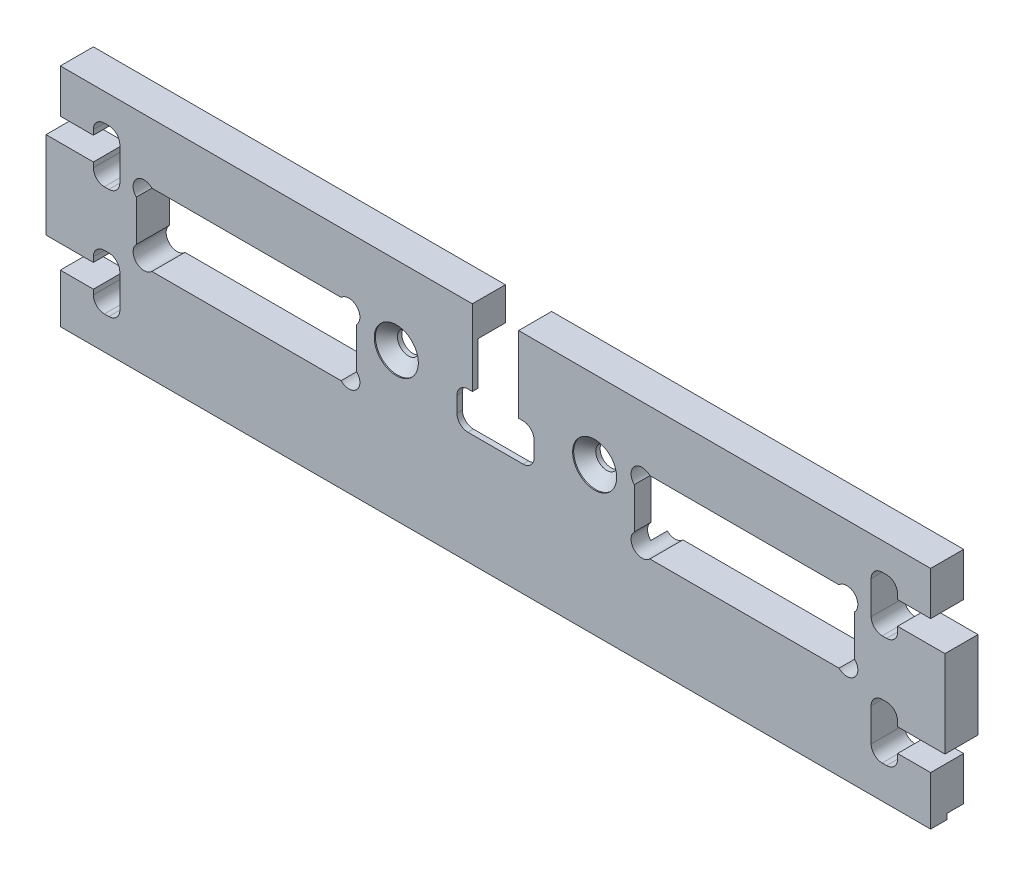
SolidWorks part; units mm, degrees
ref_plane "Front Plane" through (0, 0, 0) normal (0, 0, 1) x (1, 0, 0)
ref_plane "Top Plane" through (0, 0, 0) normal (0, 1, 0) x (1, 0, 0)
ref_plane "Right Plane" through (0, 0, 0) normal (1, 0, 0) x (0, 0, -1)
sketch "Sketch1" plane through (0, 0, 0) normal (0, 0, 1) x (1, 0, 0)
  line L0 (-39.5, 0) -> (39.5, 0) construction
  line L1 (-39.5, 10) -> (39.5, 10)
  line L2 (-39.5, 10) -> (-39.5, -10)
  line L3 (-39.5, -10) -> (39.5, -10)
  line L4 (39.5, 10) -> (39.5, -10)
  line L5 (-39.5, 10) -> (39.5, -10) construction
  line L6 (-39.5, -10) -> (39.5, 10) construction
  line L7 (0, 10) -> (0, -10) construction
  line L9 (-40.8, -3.95) -> (-39.5, -3.95)
  line L10 (-40.8, -3.95) -> (-40.8, 3.95)
  line L11 (-40.8, 3.95) -> (-39.5, 3.95)
  line L12 (-39.5, -3.95) -> (-39.5, 3.95)
  line L13 (-40.8, -3.95) -> (-39.5, 3.95) construction
  line L14 (-40.8, 3.95) -> (-39.5, -3.95) construction
  line L16 (40.8, 3.95) -> (39.5, 3.95)
  line L17 (40.8, -3.95) -> (40.8, 3.95)
  line L18 (40.8, -3.95) -> (39.5, -3.95)
  line L19 (-39.5, 5) -> (39.5, 5) construction
  line L20 (-35.3, 7.5) -> (-35.3, 2.5) construction
  line L21 (-36.5, 3.95) -> (-39.5, 3.95)
  line L22 (-36.5, 3.95) -> (-36.5, 6.05)
  line L23 (-36.5, 6.05) -> (-39.5, 6.05)
  line L24 (-39.5, 3.95) -> (-39.5, 6.05)
  line L25 (-36.5, 3.95) -> (-39.5, 6.05) construction
  line L26 (-36.5, 6.05) -> (-39.5, 3.95) construction
  line L27 (-34.1, 7.5) -> (-36.5, 7.5)
  line L28 (-34.1, 7.5) -> (-34.1, 2.5)
  line L29 (-34.1, 2.5) -> (-36.5, 2.5)
  line L30 (-36.5, 7.5) -> (-36.5, 2.5)
  line L31 (-34.1, 7.5) -> (-36.5, 2.5) construction
  line L32 (-34.1, 2.5) -> (-36.5, 7.5) construction
  line L33 (-34.1, -7.5) -> (-36.5, -7.5)
  line L34 (-34.1, -7.5) -> (-34.1, -2.5)
  line L35 (-34.1, -2.5) -> (-36.5, -2.5)
  line L36 (-36.5, -7.5) -> (-36.5, -2.5)
  line L37 (-36.5, -3.95) -> (-39.5, -3.95)
  line L38 (-36.5, -6.05) -> (-39.5, -6.05)
  line L39 (36.5, 3.95) -> (39.5, 3.95)
  line L40 (36.5, 6.05) -> (39.5, 6.05)
  line L41 (36.5, 7.5) -> (36.5, 2.5)
  line L42 (34.1, 7.5) -> (36.5, 7.5)
  line L43 (34.1, 7.5) -> (34.1, 2.5)
  line L44 (34.1, 2.5) -> (36.5, 2.5)
  line L45 (34.1, -2.5) -> (36.5, -2.5)
  line L46 (34.1, -7.5) -> (34.1, -2.5)
  line L47 (34.1, -7.5) -> (36.5, -7.5)
  line L48 (36.5, -7.5) -> (36.5, -2.5)
  line L49 (36.5, -6.05) -> (39.5, -6.05)
  line L50 (36.5, -3.95) -> (39.5, -3.95)
  point P0 (0, 0)
  point P10 (-40.15, 0)
  point P15 (-38, 5)
  point P35 (-35.3, 5)
  dimension "D1" = 79
  dimension "D2" = 20
  dimension "D4" = 1.3
  dimension "D7" = 5
  dimension "D8" = 2.1
  dimension "D9" = 3
  dimension "D10" = 2.4
  dimension "D11" = 5
extrude "Base shape" add sketch "Sketch1" along normal blind 3 contours L4 L1 L2 L3 | L9 L2 L11 L10 | L16 L4 L18 L17 region at (0, 0, 0) region at (-40.15, 0, 0) region at (40.15, 0, 0)
sketch "Sketch4" plane through (0, -10, 0) normal (0, -1, 0) x (1, 0, 0)
  line L0 (39.5, 3) -> (39.5, 0) construction
  line L1 (-39.5, 3) -> (39.5, 3)
  line L2 (-39.5, 3) -> (-39.5, 1.5)
  line L3 (-39.5, 1.5) -> (39.5, 1.5)
  line L4 (39.5, 3) -> (39.5, 1.5)
extrude "Floor lip" add sketch "Sketch4" along normal blind 0.5
sketch "Sketch6" plane through (0, 0, 0) normal (0, 0, -1) x (-1, 0, 0)
  line L0 (0, 0) -> (0, -10) construction
  line L1 (39.5, -10) -> (-39.5, -10) construction
  line L2 (-4, -10) -> (4, -10) construction
  line L3 (39.5, -10) -> (-39.5, -10) construction
  line L4 (-4, -9) -> (4, -9)
  line L5 (-4, -11) -> (4, -11)
  arc A0 (-4, -9) -> (-4, -11) centre (-4, -10) ccw
  arc A1 (4, -11) -> (4, -9) centre (4, -10) ccw
  point P9 (0, -10)
  dimension "D1" = 2
  dimension "D2" = 8
extrude "Nail cutout" cut sketch "Sketch6" against normal up to surface (1.5 mm away) up to face at (0, -10.25, 1.5)
sketch "Sketch3" plane through (-40.8, 0, 0) normal (-1, 0, 0) x (0, 0, 1)
  line L0 (0, 6.05) -> (3, 3.95) construction
  line L1 (0, 6.05) -> (3, 6.05)
  line L2 (0, 6.05) -> (0, 3.95)
  line L3 (0, 3.95) -> (3, 3.95)
  line L4 (3, 6.05) -> (3, 3.95)
  line L5 (0, -3.95) -> (3, -6.05) construction
  line L6 (0, -3.95) -> (3, -3.95)
  line L7 (0, -3.95) -> (0, -6.05)
  line L8 (0, -6.05) -> (3, -6.05)
  line L9 (3, -3.95) -> (3, -6.05)
  point P6 (1.5, 5)
  point P13 (1.5, -5)
ref_axis "Tap axis top" through (-53.7846, 5, 1.5) along (1, 0, 0)
ref_axis "Tap axis bottom" through (-54.2844, -5, 1.5) along (1, 0, 0)
fillet "Mill fillets" radius 1 16 edges at (36.5, -7.5, 1.5) (36.5, 2.5, 1.5) (34.1, 2.5, 1.5) (34.1, -7.5, 1.5) (36.5, -2.5, 1.5) (36.5, 7.5, 1.5) (34.1, -2.5, 1.5) (34.1, 7.5, 1.5) (-36.5, -2.5, 1.5) (-34.1, -2.5, 1.5) (-34.1, -7.5, 1.5) (-36.5, -7.5, 1.5) (-36.5, 2.5, 1.5) (-34.1, 2.5, 1.5) (-34.1, 7.5, 1.5) (-36.5, 7.5, 1.5)
sketch "Sketch8" [suppressed] plane through (0, 0, 3) normal (0, 0, 1) x (1, 0, 0)
  line L0 (-40.8, 0) -> (40.8, 0) construction
  line L1 (-40.8, -3.95) -> (-40.8, 3.95) construction
  line L2 (40.8, -3.95) -> (40.8, 3.95) construction
  line L4 (-24.5, 5.15) -> (24.5, 5.15)
  line L5 (-25.5, 4.15) -> (-25.5, -4.15)
  line L6 (-24.5, -5.15) -> (24.5, -5.15)
  line L7 (25.5, 4.15) -> (25.5, -4.15)
  line L8 (-25.5, 5.15) -> (25.5, -5.15) construction
  line L9 (-25.5, -5.15) -> (25.5, 5.15) construction
  arc A0 (24.5, -5.15) -> (25.5, -4.15) centre (24.5, -4.15) ccw
  arc A1 (24.5, 5.15) -> (25.5, 4.15) centre (24.5, 4.15) cw
  arc A2 (-25.5, -4.15) -> (-24.5, -5.15) centre (-24.5, -4.15) ccw
  arc A3 (-24.5, 5.15) -> (-25.5, 4.15) centre (-24.5, 4.15) ccw
  point P6 (0, 0)
  dimension "D3" = 1
  dimension "D1" = 51
  dimension "D2" = 10.3
extrude "Led strip pocket" [suppressed] cut sketch "Sketch8" against normal offset from surface (2.5 mm away) 0.5 up to face at (0, -0.6712, 0)
sketch "Sketch9" [suppressed] plane through (0, 0, 0.5) normal (0, 0, 1) x (1, 0, 0)
  line L0 (-19.5, 5.15) -> (-19.5, -5.15)
  line L1 (0, 5.15) -> (0, -5.15) construction
  line L2 (19.5, 5.15) -> (19.5, -5.15)
  line L3 (-25.5, -2.978) -> (25.5, -2.978) construction
  line L4 (25.5, -4.15) -> (25.5, 4.15)
  line L5 (24.5, 5.15) -> (-24.5, 5.15)
  line L6 (-25.5, 4.15) -> (-25.5, -4.15)
  line L7 (-24.5, -5.15) -> (24.5, -5.15)
  line L8 (25.5, -4.15) -> (25.5, 4.15)
  line L9 (24.5, 5.15) -> (-24.5, 5.15)
  line L10 (-25.5, 4.15) -> (-25.5, -4.15)
  line L11 (-24.5, -5.15) -> (24.5, -5.15)
  circle A0 centre (-12.7, -2.978) radius 1
  circle A1 centre (12.7, -2.978) radius 1
  arc A4 (24.5, -5.15) -> (25.5, -4.15) centre (24.5, -4.15) ccw
  arc A5 (25.5, 4.15) -> (24.5, 5.15) centre (24.5, 4.15) ccw
  arc A6 (-24.5, 5.15) -> (-25.5, 4.15) centre (-24.5, 4.15) ccw
  arc A7 (-25.5, -4.15) -> (-24.5, -5.15) centre (-24.5, -4.15) ccw
  arc A8 (24.5, -5.15) -> (25.5, -4.15) centre (24.5, -4.15) ccw
  arc A9 (25.5, 4.15) -> (24.5, 5.15) centre (24.5, 4.15) ccw
  arc A10 (-24.5, 5.15) -> (-25.5, 4.15) centre (-24.5, 4.15) ccw
  arc A11 (-25.5, -4.15) -> (-24.5, -5.15) centre (-24.5, -4.15) ccw
  arc M13 (24.5, -5.15) -> (25.5, -4.15) centre (24.5, -4.15) ccw
  line M14 (25.5, -4.15) -> (25.5, 4.15)
  arc M15 (25.5, 4.15) -> (24.5, 5.15) centre (24.5, 4.15) ccw
  line M16 (24.5, 5.15) -> (-24.5, 5.15)
  arc M17 (-24.5, 5.15) -> (-25.5, 4.15) centre (-24.5, 4.15) ccw
  line M18 (-25.5, 4.15) -> (-25.5, -4.15)
  arc M19 (-25.5, -4.15) -> (-24.5, -5.15) centre (-24.5, -4.15) ccw
  line M20 (-24.5, -5.15) -> (24.5, -5.15)
  dimension "D4" = 2
  dimension "D2" = 6
  dimension "D3" = 8.128
  dimension "D5" = 25.4
  dimension "D1" = 0
extrude "Led strip cuts" [suppressed] cut sketch "Sketch9" against normal up to next contours L0 M16 M17 M18 M19 M20 | L2 M16 M20 M13 M14 M15 | A0 | A1
fillet "Led strip cut fillets" [suppressed] radius 1
sketch "Sketch13" plane through (0, 0, 0) normal (0, 0, -1) x (-1, 0, 0)
  line L0 (0, 15.8648) -> (0, -21.9195) construction
  line L2 (-4.1, -5.7) -> (4.1, -5.7)
  line L3 (-5.1, -4.7) -> (-5.1, 6)
  line L4 (-4.1, 7) -> (4.1, 7)
  line L5 (5.1, -4.7) -> (5.1, 6)
  line L6 (-5.1, -5.7) -> (5.1, 7) construction
  line L7 (-5.1, 7) -> (5.1, -5.7) construction
  line L10 (39.5, 10) -> (-39.5, 10) construction
  arc A0 (-4.1, -5.7) -> (-5.1, -4.7) centre (-4.1, -4.7) cw
  arc A1 (4.1, -5.7) -> (5.1, -4.7) centre (4.1, -4.7) ccw
  arc A4 (5.1, 6) -> (4.1, 7) centre (4.1, 6) ccw
  arc A5 (-5.1, 6) -> (-4.1, 7) centre (-4.1, 6) cw
  point P1 (0, 0.65)
  point P8 (0, 0)
  point P9 (5.5684, 9.0125)
  point P16 (0, 0)
  point P17 (0, 0)
  dimension "D4" = 1
  dimension "D5" = 1
  dimension "D1" = 10.2
  dimension "D2" = 12.7
  dimension "D3" = 3
extrude "Bumper mount inner cut" cut sketch "Sketch13" against normal offset from surface (2.5 mm away) 0.5 up to face at (0, -0.0192, 3)
sketch "Sketch14" plane through (0, 0, 0) normal (0, 0, -1) x (-1, 0, 0)
  line L1 (0, 12.9528) -> (0, -14.0841) construction
  line L2 (4.1, 7) -> (-4.1, 7) construction
  line L3 (-4.1, -5.7) -> (4.1, -5.7) construction
  line L4 (-11.6, 7) -> (11.6, 7)
  line L5 (-12.6, 6) -> (-12.6, -4.7)
  line L6 (-11.6, -5.7) -> (11.6, -5.7)
  line L7 (12.6, 6) -> (12.6, -4.7)
  line L8 (-12.6, 7) -> (12.6, -5.7) construction
  line L9 (-12.6, -5.7) -> (12.6, 7) construction
  arc A1 (11.6, -5.7) -> (12.6, -4.7) centre (11.6, -4.7) ccw
  arc A2 (-12.6, -4.7) -> (-11.6, -5.7) centre (-11.6, -4.7) ccw
  arc A3 (11.6, 7) -> (12.6, 6) centre (11.6, 6) cw
  arc A4 (-12.6, 6) -> (-11.6, 7) centre (-11.6, 6) cw
  point P6 (0, 0.65)
  dimension "D2" = 1
  dimension "D3" = 1
  dimension "D1" = 25.2
extrude "Bumper mount outer cut" cut sketch "Sketch14" against normal blind 1.5
sketch "Sketch15" plane through (0, 0, 1.5) normal (0, 0, -1) x (-1, 0, 0)
  line L0 (-12.6, 2.9) -> (12.6, 2.9) construction
  line L3 (0, 16.4744) -> (0, -20.0474) construction
  line L7 (-12.6, 6) -> (-12.6, -4.7) construction
  line L8 (12.6, -4.7) -> (12.6, 6) construction
  line L11 (-4.1, 7) -> (-11.6, 7) construction
  circle A0 centre (-9, 2.9) radius 1
  circle A1 centre (9, 2.9) radius 1
  point P5 (10, 7)
  point P13 (0, 0)
  point P19 (0, 0)
  point P22 (0, 0)
  point P24 (0, 0)
  point P25 (8.6174, -5.7)
  point P26 (0, 0)
  point P27 (0, 0)
  point P28 (0, 0)
  point P29 (0, 0)
  point P30 (13.4221, 7)
  dimension "D1" = 18
  dimension "D2" = 2
  dimension "D3" = 4.1
extrude "Bumper mount screw holes" cut sketch "Sketch15" against normal up to next
sketch "Sketch16" plane through (0, 0, 2.5) normal (0, 0, -1) x (-1, 0, 0)
  line L0 (-5.1, 1.4) -> (5.1, 1.4) construction
  line L3 (0, 7) -> (0, -4.2) construction
  line L4 (-2.5, 3.1) -> (2.5, 3.1)
  line L5 (-3.5, 2.1) -> (-3.5, 0.7)
  line L6 (-2.5, -0.3) -> (2.5, -0.3)
  line L7 (3.5, 2.1) -> (3.5, 0.7)
  line L8 (-3.5, 3.1) -> (3.5, -0.3) construction
  line L9 (-3.5, -0.3) -> (3.5, 3.1) construction
  line L11 (-5.1, 6) -> (-5.1, -4.7) construction
  line L13 (4.1, 7) -> (-4.1, 7) construction
  arc A0 (2.5, -0.3) -> (3.5, 0.7) centre (2.5, 0.7) ccw
  arc A1 (-3.5, 0.7) -> (-2.5, -0.3) centre (-2.5, 0.7) ccw
  arc A2 (-2.5, 3.1) -> (-3.5, 2.1) centre (-2.5, 2.1) ccw
  arc A3 (2.5, 3.1) -> (3.5, 2.1) centre (2.5, 2.1) cw
  point P2 (0, 0)
  point P5 (0, 0)
  point P6 (0, 1.4)
  point P23 (0, 0)
  point P24 (0, 7.9459)
  point P29 (0, 0)
  dimension "D3" = 1
  dimension "D1" = 7
  dimension "D2" = 3.4
  dimension "D4" = 11.2
extrude "Bumper body cut" cut sketch "Sketch16" against normal up to next
hole_wizard "Bumper screw countersunks" positions "Sketch17" profile "Sketch18" countersink size "M2" standard "ANSI Metric" end condition through all
sketch "Sketch17" plane through (0, 0, 3) normal (0, 0, 1) x (1, 0, 0)
  point P0 (9, 2.9)
  point P3 (-9, 2.9)
sketch "Sketch18" plane through (9, 2.9, 3) normal (1, 0, 0) x (0, -1, 0)
  line L0 (0, 0) -> (0, 3)
  line L1 (0, 3) -> (1, 3)
  line L2 (1, 3) -> (1, 1.1)
  line L3 (1, 1.1) -> (2, 0.1)
  line L4 (2, 0.1) -> (2, 0)
  line L6 (2, 0) -> (0, 0)
  line L7 (-1, 1.1) -> (-2, 0.1) construction
  line L11 (0, -6.35) -> (0, 107.95) construction
  dimension "Thru Hole Dia." = 2
  dimension "Thru Hole Depth" = 3
  dimension "C'Sink Dia." = 4
  dimension "C'Sink Angle" = 90
  dimension "Head Clearance" = 0.1
sketch "Sketch19" plane through (0, 0, 0) normal (0, 0, -1) x (-1, 0, 0)
  line L0 (0, 15.6498) -> (0, -12.9575) construction
  line L1 (39.5, 10) -> (-39.5, 10) construction
  line L2 (-2.1, 3.1) -> (2.1, 3.1)
  line L3 (-2.1, 3.1) -> (-2.1, 10)
  line L4 (-2.1, 10) -> (2.1, 10)
  line L5 (2.1, 3.1) -> (2.1, 10)
  line L6 (-2.1, 3.1) -> (2.1, 10) construction
  line L7 (-2.1, 10) -> (2.1, 3.1) construction
  line L8 (2.5, 3.1) -> (-2.5, 3.1) construction
  point P1 (0, 6.55)
  dimension "D1" = 4.2
extrude "Bumper insertion cut" cut sketch "Sketch19" against normal up to next
sketch "Sketch20" plane through (0, 0, 0) normal (0, 0, -1) x (-1, 0, 0)
  line L0 (-12.6, 6) -> (-12.6, -4.7) construction
  line L1 (-12.6, 4.55) -> (-32.6, 4.55)
  line L2 (-12.6, 4.55) -> (-12.6, -2)
  line L3 (-12.6, -2) -> (-32.6, -2)
  line L4 (-32.6, 4.55) -> (-32.6, -2)
  line L5 (-2.1, 10) -> (-39.5, 10) construction
  line L6 (-12.6, 4.55) -> (-19.15, -2) construction
  line L7 (-22.6, 4.55) -> (-22.6, -2) construction
  line L8 (-32.6, 1.275) -> (-12.6, 1.275) construction
  line L9 (0, 16.176) -> (0, -15.99) construction
  line L10 (12.6, 4.55) -> (12.6, -2)
  line L11 (12.6, -2) -> (32.6, -2)
  line L12 (32.6, 4.55) -> (32.6, -2)
  line L13 (12.6, 4.55) -> (32.6, 4.55)
  circle A0 centre (-13.3071, 3.8429) radius 1
  circle A1 centre (-31.8929, 3.8429) radius 1
  circle A2 centre (-13.3071, -1.2929) radius 1
  circle A3 centre (-31.8929, -1.2929) radius 1
  circle A4 centre (13.3071, 3.8429) radius 1
  circle A5 centre (13.3071, -1.2929) radius 1
  circle A6 centre (31.8929, -1.2929) radius 1
  circle A7 centre (31.8929, 3.8429) radius 1
  dimension "D5" = 2
  dimension "D1" = 20
  dimension "D2" = 5.45
  dimension "D3" = 6.55
  dimension "D4" = 45
extrude "Cut-Extrude2" cut sketch "Sketch20" against normal up to next contours L1 L4 L3 L2 | A1 | A3 | A0 | A2 | L13 L12 L11 L10 | A4 | A5 | A6 | A7
